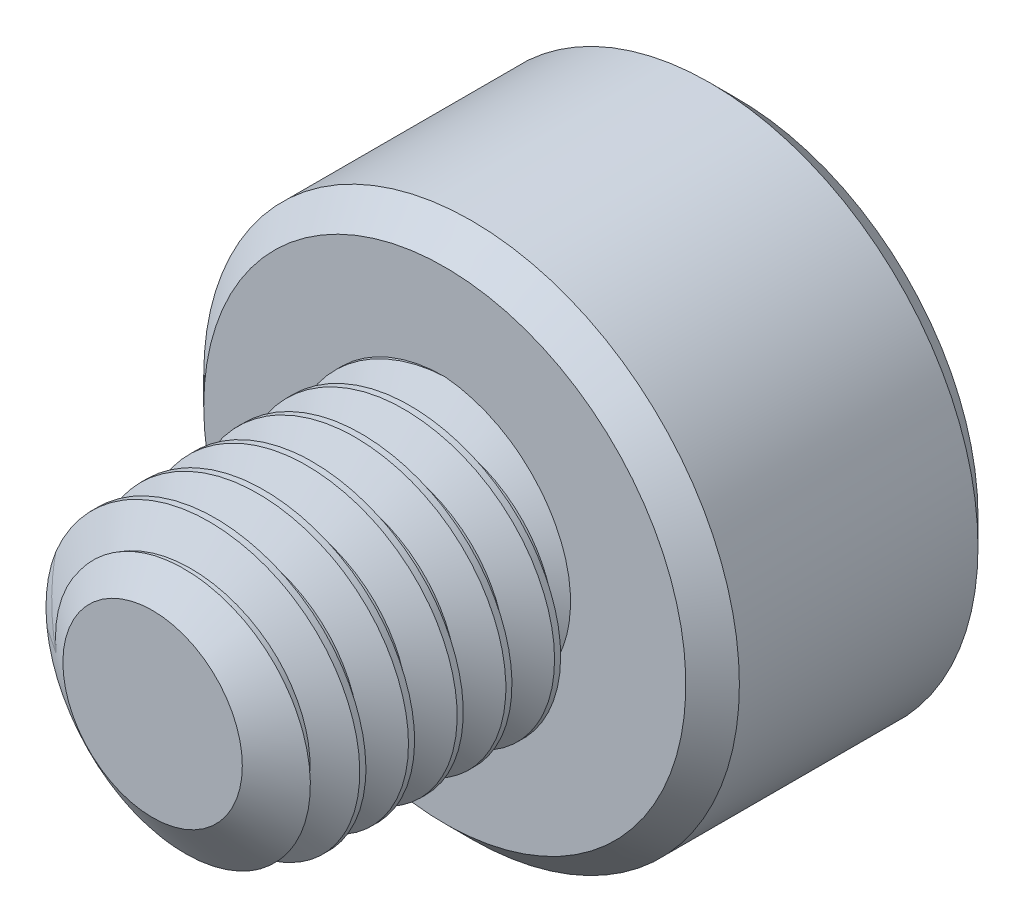
SolidWorks part; units mm, degrees
other "DetailItem1"
ref_plane "Front Plane" through (0, 0, 0) normal (0, 0, 1) x (1, 0, 0)
ref_plane "Top Plane" through (0, 0, 0) normal (0, 1, 0) x (1, 0, 0)
ref_plane "Right Plane" through (0, 0, 0) normal (1, 0, 0) x (0, 0, -1)
sketch "Sketch1" plane through (0, 0, 0) normal (0, 0, 1) x (1, 0, 0)
  circle A0 centre (0, 0) radius 1.5
  dimension "OD" = 3
extrude "Extrude1" add sketch "Sketch1" against normal blind 3
sketch "Sketch2" plane through (0, 0, 0) normal (0, 0, 1) x (1, 0, 0)
  circle A0 centre (0, 0) radius 1.5 construction
  circle A1 centre (0, 0) radius 1.5
curve "Helix/Spiral1" pitch 0.5 height 3.5 radius 1.5 centre (0, 0, 0) axis (0, 0, -1) start towards (0, 1, 0) parameters "pitch"=0.5
sketch "Sketch3" plane through (0, 0, 0) normal (1, 0, 0) x (0, 0, -1)
  line L0 (-0.4375, 1.5) -> (-0.25, 1.1752)
  line L1 (-0.25, 1.1752) -> (-0.1875, 1.1752)
  line L2 (-0.1875, 1.1752) -> (0, 1.5)
  line L3 (-0.4375, 1.5) -> (0, 1.5)
  line L4 (-0.2187, 1.5) -> (-0.2188, 1.1752) construction
  line L5 (-0.3438, 1.3376) -> (-0.0938, 1.3376) construction
  line L6 (0, 1.5) -> (0, -1.5) construction
  dimension "D1" = 0.0625
  dimension "D2" = 0.25
  dimension "D3" = 60
sweep "Cut-Sweep1" cut profiles "Sketch3" path "Helix/Spiral1" align with end faces yes
sketch "Sketch4" plane through (0, 0, 0) normal (1, 0, 0) x (0, 0, -1)
  line L0 (0.4053, 1.5) -> (0, 0.9212)
  line L1 (0, 0.9212) -> (0, 1.5)
  line L2 (0.4053, 1.5) -> (0, 1.5)
  line L3 (-0.4375, 1.5) -> (0, 1.5) construction
  line L4 (0, 0) -> (7.0209, 0) construction
  dimension "D1" = 55
  dimension "D2" = 0.254
revolve "Cut-Revolve1" cut sketch "Sketch4" angle 360 about L4
sketch "Sketch6" plane through (0, 0, -3) normal (0, 0, -1) x (-1, 0, 0)
  circle A0 centre (0, 0) radius 2.75
  dimension "head dia" = 5.5
extrude "Extrude2" add sketch "Sketch6" along normal blind 3
sketch "Sketch7" plane through (0, 0, -6) normal (0, 0, -1) x (-1, 0, 0)
  line L1 (0, 1.4434) -> (-1.25, 0.7217)
  line L2 (-1.25, 0.7217) -> (-1.25, -0.7217)
  line L3 (-1.25, -0.7217) -> (0, -1.4434)
  line L4 (0, -1.4434) -> (1.25, -0.7217)
  line L5 (1.25, -0.7217) -> (1.25, 0.7217)
  line L6 (1.25, 0.7217) -> (0, 1.4434)
  circle A0 centre (0, 0) radius 1.25 construction
  dimension "hex dia" = 2.5
extrude "Cut-Extrude1" cut sketch "Sketch7" against normal blind 1.875
sketch "Sketch8" plane through (0, 0, -6) normal (0, 0, -1) x (-1, 0, 0)
  circle A0 centre (0, 0) radius 1.4434
extrude "Cut-Extrude2" cut sketch "Sketch8" against normal through all draft 45
chamfer "Chamfer1" distance 0.275 angle 45 2 edges at (-2.75, 0, -6) (-2.75, 0, -3)
sketch "Sketch10" plane through (0, 0, -3) normal (0, 0, 1) x (1, 0, 0)
  circle A1 centre (0, 0) radius 1.5
  circle A2 centre (0, 0) radius 1.5
  dimension "D1" = 0
ref_plane "Plane1" through (0, 0, 0) normal (0, 0, 1) x (1, 0, 0)
extrude "partial thread" [suppressed] add sketch "Sketch10" along normal up to surface (4 mm away) separate body up to plane "Plane1"
chamfer "Chamfer2" [suppressed] distance 0.06 angle 45
combine bodies "Combine1" [suppressed] operation type add bodies to combine 107 108
sketch "Sketch9" plane through (0, 0, 0) normal (1, 0, 0) x (0, 0, -1)
  line L0 (0, 1.5) -> (0, -1.5) construction
  line L1 (1.25, 1.5) -> (1.25, -1.5) construction
  dimension "D1" = 1.25
equation "\"D3@Helix/Spiral1\" = \"screw length@Extrude1\"+\"pitch@Helix/Spiral1\""
equation "\"D1@Sketch3\" = \"pitch@Helix/Spiral1\"*.125"
equation "\"D2@Sketch3\" = \"pitch@Helix/Spiral1\"*.5"
equation "\"D1@Cut-Extrude1\" = \"hex dia@Sketch7\"*.75"
equation "\"D1@Chamfer1\" = \"head dia@Sketch6\"*.05"
equation "\"D1@Sketch9\" = \"pitch@Helix/Spiral1\"*2.5"
equation "\"D1@Chamfer2\"=\"OD@Sketch1\"*.02"
